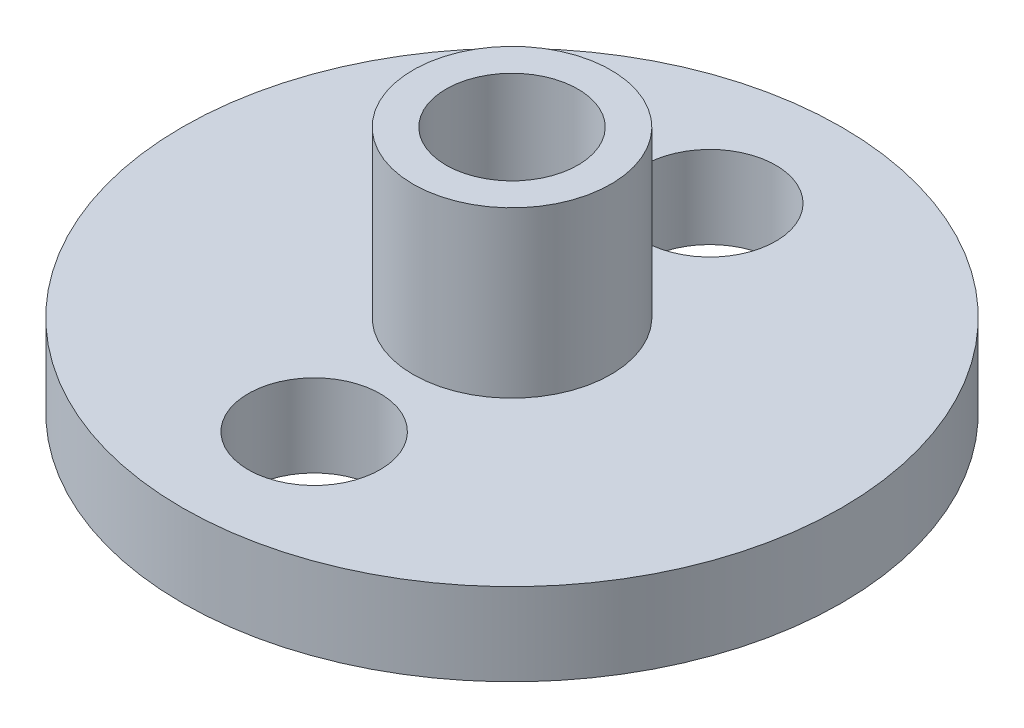
SolidWorks part; units mm, degrees
material "AISI 1020"
ref_plane "Front Plane" through (0, 0, 0) normal (0, 0, 1) x (1, 0, 0)
ref_plane "Top Plane" through (0, 0, 0) normal (0, 1, 0) x (1, 0, 0)
ref_plane "Right Plane" through (0, 0, 0) normal (1, 0, 0) x (0, 0, -1)
sketch "Sketch1" plane through (0, 0, 0) normal (0, 1, 0) x (1, 0, 0)
  circle A0 centre (0, 0) radius 20
  circle A2 centre (0, 12) radius 4
  circle A3 centre (0, -12) radius 4
  dimension "D1" = 40
  dimension "D3" = 4
  dimension "D4" = 4
  dimension "D5" = 12
  dimension "D6" = 12
extrude "Boss-Extrude1" add sketch "Sketch1" along normal blind 5
sketch "Sketch2" plane through (0, 5, 0) normal (0, 1, 0) x (1, 0, 0)
  circle A0 centre (0, 0) radius 6
  circle A1 centre (0, 0) radius 4
  dimension "D1" = 12
  dimension "D2" = 8
extrude "Boss-Extrude2" add sketch "Sketch2" along normal blind 10
sketch "Sketch3" plane through (0, 0, 0) normal (0, -1, 0) x (1, 0, 0)
  line L1 (0, 20) -> (0, -20) construction
  circle A1 centre (0, 0) radius 20 construction
  point P5 (0, 0)
